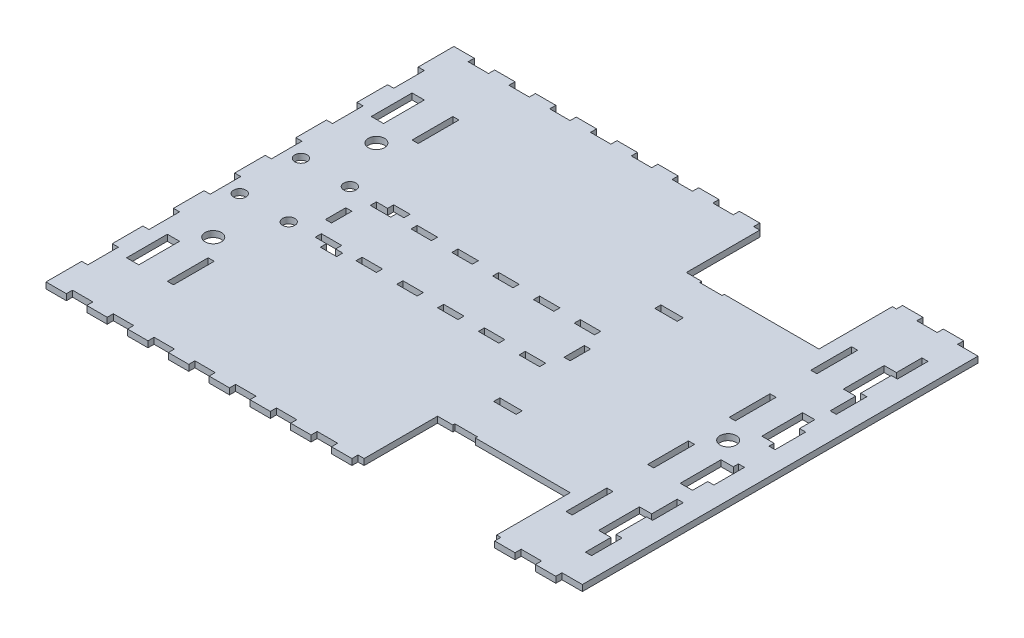
SolidWorks part; units mm, degrees
ref_plane "Front Plane" through (0, 0, 0) normal (0, 0, 1) x (1, 0, 0)
ref_plane "Top Plane" through (0, 0, 0) normal (0, 1, 0) x (1, 0, 0)
ref_plane "Right Plane" through (0, 0, 0) normal (1, 0, 0) x (0, 0, -1)
sketch "Sketch3" plane through (0, 0, 0) normal (0, 1, 0) x (1, 0, 0)
  line L0 (0, 0) -> (-300, 0) construction
  line L1 (-300, -97) -> (-300, 97)
  line L2 (-290, 100) -> (-300, 100)
  line L3 (-290, 97) -> (-290, 100)
  line L4 (-280, 97) -> (-290, 97)
  line L5 (-300, 100) -> (-300, 97)
  line L6 (-270, 100) -> (-280, 100)
  line L7 (-270, 97) -> (-270, 100)
  line L8 (-260, 97) -> (-270, 97)
  line L9 (-280, 100) -> (-280, 97)
  line L10 (-250, 100) -> (-260, 100)
  line L11 (-250, 97) -> (-250, 100)
  line L12 (-240, 97) -> (-250, 97)
  line L13 (-260, 100) -> (-260, 97)
  line L14 (-150, -100) -> (-150, 100) construction
  line L15 (-230, 100) -> (-240, 100)
  line L16 (-230, 97) -> (-230, 100)
  line L17 (-220, 97) -> (-230, 97)
  line L18 (-240, 100) -> (-240, 97)
  line L19 (-210, 100) -> (-220, 100)
  line L20 (-210, 97) -> (-210, 100)
  line L21 (-200, 97) -> (-210, 97)
  line L22 (-40, 97) -> (-40, -97)
  line L23 (-50, 37.5) -> (-53, 37.5)
  line L24 (-50, 7.5) -> (-53, 7.5)
  line L25 (-50, -45.947) -> (-50, 45.947) construction
  line L26 (-247, 37.5) -> (-250, 37.5) construction
  line L27 (-247, 7.5) -> (-250, 7.5) construction
  line L28 (-247, 48.5) -> (-247, -48.5) construction
  line L29 (-247, 48.5) -> (-223, 48.5) construction
  line L30 (-223, 48.5) -> (-223, -48.5) construction
  line L31 (-210, 15) -> (-90, 15) construction
  line L32 (-90, 15) -> (-90, 5) construction
  line L33 (-50, 7.5) -> (-50, 22.5)
  line L34 (-220, 100) -> (-220, 97)
  line L35 (-190, 100) -> (-200, 100)
  line L36 (-190, 97) -> (-190, 100)
  line L37 (-180, 97) -> (-190, 97)
  line L38 (-200, 100) -> (-200, 97)
  line L39 (-170, 100) -> (-180, 100)
  line L40 (-170, 97) -> (-170, 100)
  line L41 (-160, 97) -> (-170, 97)
  line L42 (-180, 100) -> (-180, 97)
  line L43 (-150, 100) -> (-160, 100)
  line L44 (-150, 97) -> (-150, 100)
  line L45 (-140, 97) -> (-150, 97)
  line L46 (-160, 100) -> (-160, 97)
  line L47 (-130, 100) -> (-140, 100)
  line L48 (-130, 97) -> (-130, 100)
  line L49 (-120, 97) -> (-130, 97)
  line L50 (-140, 100) -> (-140, 97)
  line L51 (-110, 100) -> (-120, 100)
  line L52 (-110, 97) -> (-110, 100)
  line L53 (-100, 97) -> (-110, 97)
  line L54 (-120, 100) -> (-120, 97)
  line L55 (-90, 100) -> (-100, 100)
  line L56 (-90, 97) -> (-90, 100)
  line L57 (-80, 97) -> (-90, 97)
  line L58 (-100, 100) -> (-100, 97)
  line L59 (-70, 100) -> (-80, 100)
  line L60 (-70, 97) -> (-70, 100)
  line L61 (-60, 97) -> (-70, 97)
  line L62 (-80, 100) -> (-80, 97)
  line L63 (-50, 100) -> (-60, 100)
  line L64 (-50, 97) -> (-50, 100)
  line L65 (-40, 97) -> (-50, 97)
  line L66 (-60, 100) -> (-60, 97)
  line L67 (-50, 22.5) -> (-53, 22.5)
  line L68 (-210, -15) -> (-90, -15) construction
  line L69 (-53, 7.5) -> (-53, 22.5)
  line L70 (-50, 37.5) -> (-50, 52.5)
  line L71 (-50, 52.5) -> (-53, 52.5)
  line L72 (-53, 37.5) -> (-53, 52.5)
  line L73 (-50, 67.5) -> (-53, 67.5)
  line L74 (-50, 67.5) -> (-50, 82.5)
  line L75 (-50, 82.5) -> (-53, 82.5)
  line L76 (-60, -100) -> (-60, -97)
  line L77 (-40, -97) -> (-50, -97)
  line L78 (-50, -97) -> (-50, -100)
  line L79 (-50, -100) -> (-60, -100)
  line L80 (-80, -100) -> (-80, -97)
  line L81 (-60, -97) -> (-70, -97)
  line L82 (-70, -97) -> (-70, -100)
  line L83 (-70, -100) -> (-80, -100)
  line L84 (-100, -100) -> (-100, -97)
  line L85 (-80, -97) -> (-90, -97)
  line L86 (-90, -97) -> (-90, -100)
  line L87 (-90, -100) -> (-100, -100)
  line L88 (-120, -100) -> (-120, -97)
  line L89 (-100, -97) -> (-110, -97)
  line L90 (-110, -97) -> (-110, -100)
  line L91 (-110, -100) -> (-120, -100)
  line L92 (-140, -100) -> (-140, -97)
  line L93 (-120, -97) -> (-130, -97)
  line L94 (-130, -97) -> (-130, -100)
  line L95 (-130, -100) -> (-140, -100)
  line L96 (-160, -100) -> (-160, -97)
  line L97 (-140, -97) -> (-150, -97)
  line L98 (-150, -97) -> (-150, -100)
  line L99 (-150, -100) -> (-160, -100)
  line L100 (-180, -100) -> (-180, -97)
  line L101 (-160, -97) -> (-170, -97)
  line L102 (-170, -97) -> (-170, -100)
  line L103 (-170, -100) -> (-180, -100)
  line L104 (-200, -100) -> (-200, -97)
  line L105 (-180, -97) -> (-190, -97)
  line L106 (-190, -97) -> (-190, -100)
  line L107 (-190, -100) -> (-200, -100)
  line L108 (-247, -48.5) -> (-223, -48.5) construction
  line L109 (-247, 7.5) -> (-247, 22.5) construction
  line L110 (-220, -100) -> (-220, -97)
  line L111 (-53, 67.5) -> (-53, 82.5)
  line L112 (-53, -67.5) -> (-53, -82.5)
  line L113 (-50, -82.5) -> (-53, -82.5)
  line L114 (-200, -97) -> (-210, -97)
  line L115 (-210, -97) -> (-210, -100)
  line L116 (-210, -100) -> (-220, -100)
  line L117 (-240, -100) -> (-240, -97)
  line L118 (-220, -97) -> (-230, -97)
  line L119 (-230, -97) -> (-230, -100)
  line L120 (-230, -100) -> (-240, -100)
  line L121 (-50, -67.5) -> (-50, -82.5)
  line L122 (-260, -100) -> (-260, -97)
  line L123 (-240, -97) -> (-250, -97)
  line L124 (-250, -97) -> (-250, -100)
  line L125 (-250, -100) -> (-260, -100)
  line L126 (-280, -100) -> (-280, -97)
  line L127 (-260, -97) -> (-270, -97)
  line L128 (-270, -97) -> (-270, -100)
  line L129 (-270, -100) -> (-280, -100)
  line L130 (-300, -100) -> (-300, -97)
  line L131 (-210, 15) -> (-210, -15) construction
  line L132 (-253, -15) -> (-243, -15)
  line L133 (-233, -15) -> (-223, -15)
  line L188 (-247, 22.5) -> (-250, 22.5) construction
  line L189 (-250, 7.5) -> (-250, 22.5) construction
  line L190 (-247, 37.5) -> (-247, 52.5) construction
  line L191 (-247, 52.5) -> (-250, 52.5) construction
  line L192 (-250, 37.5) -> (-250, 52.5) construction
  line L193 (-247, 67.5) -> (-250, 67.5) construction
  line L194 (-247, 67.5) -> (-247, 82.5) construction
  line L195 (-247, 82.5) -> (-250, 82.5) construction
  line L196 (-250, 67.5) -> (-250, 82.5) construction
  line L197 (-250, -67.5) -> (-250, -82.5) construction
  line L198 (-247, -82.5) -> (-250, -82.5) construction
  line L199 (-247, -67.5) -> (-247, -82.5) construction
  line L200 (-247, -67.5) -> (-250, -67.5) construction
  line L201 (-250, -37.5) -> (-250, -52.5) construction
  line L202 (-247, -52.5) -> (-250, -52.5) construction
  line L203 (-247, -37.5) -> (-247, -52.5) construction
  line L204 (-250, -7.5) -> (-250, -22.5) construction
  line L205 (-247, -22.5) -> (-250, -22.5) construction
  line L206 (-247, -7.5) -> (-247, -22.5) construction
  line L207 (-247, -7.5) -> (-250, -7.5) construction
  line L208 (-247, -37.5) -> (-250, -37.5) construction
  line L209 (-50, -67.5) -> (-53, -67.5)
  line L210 (-53, -37.5) -> (-53, -52.5)
  line L211 (-50, -52.5) -> (-53, -52.5)
  line L212 (-50, -37.5) -> (-50, -52.5)
  line L213 (-53, -7.5) -> (-53, -22.5)
  line L214 (-50, -22.5) -> (-53, -22.5)
  line L215 (-50, -7.5) -> (-50, -22.5)
  line L216 (-50, -7.5) -> (-53, -7.5)
  line L217 (-50, -37.5) -> (-53, -37.5)
  line L218 (-210, 0) -> (-258, 0)
  line L219 (-258, -5) -> (-255, -5)
  line L220 (-163, 15) -> (-173, 15)
  line L221 (-243, -12) -> (-243, -15)
  line L222 (-143, 15) -> (-143, 12)
  line L223 (-173, -15) -> (-173, -12)
  line L224 (-163, -15) -> (-173, -15)
  line L225 (-183, 12) -> (-183, 15)
  line L226 (-153, 15) -> (-153, 12)
  line L227 (-163, -12) -> (-163, -15)
  line L228 (-243, -12) -> (-253, -12)
  line L229 (-193, -15) -> (-193, -12)
  line L230 (-258, 5) -> (-255, 5)
  line L231 (-280, -97) -> (-290, -97)
  line L232 (-290, -97) -> (-290, -100)
  line L233 (-290, -100) -> (-300, -100)
  line L234 (-143, 15) -> (-153, 15)
  line L235 (-203, -12) -> (-213, -12)
  line L236 (-213, -15) -> (-213, -12)
  line L237 (-233, -15) -> (-233, -12)
  line L238 (-138, 5) -> (-141, 5)
  line L239 (-243, 12) -> (-243, 15)
  line L240 (-223, 12) -> (-223, 15)
  line L241 (-203, 12) -> (-213, 12)
  line L242 (-153, -15) -> (-153, -12)
  line L243 (-253, 15) -> (-253, 12)
  line L244 (-163, 12) -> (-163, 15)
  line L245 (-141, 5) -> (-141, -5)
  line L246 (-143, -15) -> (-143, -12)
  line L247 (-223, -12) -> (-233, -12)
  line L248 (-258, 15) -> (-258, -15) construction
  line L249 (-233, 15) -> (-233, 12)
  line L250 (-223, 15) -> (-233, 15)
  line L251 (-138, -5) -> (-141, -5)
  line L252 (-183, -15) -> (-193, -15)
  line L253 (-203, 15) -> (-213, 15)
  line L254 (-138, 5) -> (-138, -5)
  line L255 (-258, -15) -> (-138, -15) construction
  line L256 (-255, 5) -> (-255, -5)
  line L257 (-258, 5) -> (-258, -5)
  line L258 (-258, 15) -> (-138, 15) construction
  line L259 (-193, 15) -> (-193, 12)
  line L260 (-163, 12) -> (-173, 12)
  line L261 (-203, -15) -> (-213, -15)
  line L262 (-243, 12) -> (-253, 12)
  line L263 (-183, 15) -> (-193, 15)
  line L264 (-143, 12) -> (-153, 12)
  line L265 (-243, 15) -> (-253, 15)
  line L266 (-213, 15) -> (-213, 12)
  line L267 (-173, 15) -> (-173, 12)
  line L268 (-223, -12) -> (-223, -15)
  line L269 (-143, -12) -> (-153, -12)
  line L270 (-143, -15) -> (-153, -15)
  line L271 (-183, -12) -> (-193, -12)
  line L272 (-203, -12) -> (-203, -15)
  line L273 (-203, 12) -> (-203, 15)
  line L274 (-183, -12) -> (-183, -15)
  line L275 (-253, -15) -> (-253, -12)
  line L276 (-223, 12) -> (-233, 12)
  line L277 (-183, 12) -> (-193, 12)
  line L278 (-163, -12) -> (-173, -12)
  circle A0 centre (-290, 15) radius 3
  circle A1 centre (-266, 15) radius 3
  circle A2 centre (-266, -15) radius 3
  circle A3 centre (-290, -15) radius 3
  point P31 (-250, 36)
  point P80 (-91.5, 0)
  point P82 (-150, 0)
  point P126 (-223, 0)
  point P128 (-250, 18)
  point P129 (-50, 0)
  point P150 (-150, -15)
  point P151 (-150, 15)
  point P183 (-208.5, 0)
  point P212 (-223, 18)
  point P218 (-223, 36)
  point P235 (-198, -15)
  point P236 (-198, 15)
  dimension "D17" = 6
  dimension "D18" = 6
  dimension "D1" = 300
  dimension "D4" = 7.5
  dimension "D5" = 100
  dimension "D6" = 97
  dimension "D7" = 15
  dimension "D8" = 97
  dimension "D9" = 3
  dimension "D10" = 3
  dimension "D11" = 48.5
  dimension "D12" = 24
  dimension "D13" = 60
  dimension "D14" = 15
  dimension "D15" = 24
  dimension "D16" = 15
  dimension "D19" = 194
  dimension "D20" = 10
  dimension "D21" = 3
  dimension "D22" = 7.5
  dimension "D23" = 15
  dimension "D24" = 3
  dimension "D25" = 3
  dimension "D26" = 48
  dimension "D31" = 10
  dimension "D36" = 3
extrude "Boss-Extrude1" add sketch "Sketch3" along normal blind 3 contours L1 L116 L115 L107 L106 L83 L82 L79 L95 L98 L99 L91 L90 L86 region at (-170.2364, 0, 0)
sketch "Sketch5" plane through (0, 3, 0) normal (0, 1, 0) x (1, 0, 0)
  line L0 (-82, 0) -> (-82, 61) construction
  line L1 (-134, -60) -> (-134, -41)
  line L2 (-82, 61) -> (-128.5, 61)
  line L3 (-82, 61) -> (-82, 97)
  line L4 (-82, 97) -> (-147, 97)
  line L5 (-147, 61) -> (-147, 97)
  line L7 (-110, 100) -> (-120, 100) construction
  line L8 (-82, 0) -> (-300, 0) construction
  line L9 (-300, 100) -> (-300, -100) construction
  line L10 (-147, -61) -> (-147, -97)
  line L11 (-82, -97) -> (-147, -97)
  line L12 (-82, -61) -> (-82, -97)
  line L13 (-82, -61) -> (-128.5, -61)
  line L14 (-114.5, -61) -> (-114.5, -41) construction
  line L15 (-114.5, -41) -> (-128.5, -41) construction
  line L16 (-128.5, -41) -> (-128.5, -38)
  line L17 (-128.5, -38) -> (-139.5, -38)
  line L18 (-139.5, -38) -> (-139.5, -41)
  line L19 (-139.5, -41) -> (-128.5, -41)
  line L20 (-128.5, -61) -> (-128.5, -60)
  line L21 (-128.5, -60) -> (-139.5, -60)
  line L22 (-139.5, -60) -> (-139.5, -61)
  line L23 (-139.5, -61) -> (-147, -61)
  line L24 (-114.5, 41) -> (-128.5, 41) construction
  line L25 (-114.5, 61) -> (-114.5, 41) construction
  line L26 (-139.5, 60) -> (-139.5, 61)
  line L27 (-128.5, 60) -> (-139.5, 60)
  line L28 (-128.5, 61) -> (-128.5, 60)
  line L29 (-139.5, 41) -> (-128.5, 41)
  line L30 (-139.5, 38) -> (-139.5, 41)
  line L31 (-128.5, 38) -> (-139.5, 38)
  line L32 (-128.5, 41) -> (-128.5, 38)
  line L33 (-139.5, 61) -> (-147, 61)
  dimension "D1" = 19
  dimension "D2" = 36
  dimension "D3" = 3
  dimension "D5" = 14
  dimension "D6" = 3
  dimension "D7" = 11
  dimension "D9" = 1
extrude "Cut-Extrude2" cut sketch "Sketch5" against normal blind 10 contours L5 L2 L3 L4 | L12 L13 L10 L11 | L31 L30 L29 L32 | L17 L18 L19 L16 region at (-114.5912, 3, 78.9134) region at (-114.5912, 3, -78.9134) body kept at (-300, 0, -100)
sketch "Croquis1" plane through (0, 3, 0) normal (0, 1, 0) x (1, 0, 0)
  line L0 (-300, -67.5) -> (-300, -82.5)
  line L25 (-300, 100) -> (-300, -100) construction
  line L26 (-300, 37.5) -> (-300, 52.5)
  line L27 (-297, 37.5) -> (-300, 37.5)
  line L28 (-297, 7.5) -> (-300, 7.5)
  line L29 (-300, -7.5) -> (-297, -7.5)
  line L30 (-297, -22.5) -> (-300, -22.5)
  line L31 (-297, -7.5) -> (-297, -22.5)
  line L32 (-297, 82.5) -> (-297, 67.5)
  line L33 (-300, -22.5) -> (-300, -7.5)
  line L34 (-297, -37.5) -> (-297, -52.5)
  line L35 (-297, 67.5) -> (-300, 67.5)
  line L36 (-300, 67.5) -> (-300, 82.5)
  line L37 (-297, 52.5) -> (-297, 37.5)
  line L38 (-300, 22.5) -> (-297, 22.5)
  line L39 (-300, -37.5) -> (-297, -37.5)
  line L40 (-297, -52.5) -> (-300, -52.5)
  line L41 (-300, 52.5) -> (-297, 52.5)
  line L42 (-300, -52.5) -> (-300, -37.5)
  line L43 (-300, 82.5) -> (-297, 82.5)
  line L44 (-297, 22.5) -> (-297, 7.5)
  line L45 (-300, 7.5) -> (-300, 22.5)
  line L46 (-300, -67.5) -> (-297, -67.5)
  line L47 (-297, -67.5) -> (-297, -82.5)
  line L48 (-297, -82.5) -> (-300, -82.5)
  dimension "D1" = 15
  dimension "D2" = 15
extrude "Cortar-Extruir1" cut sketch "Croquis1" against normal blind 10
sketch "Croquis2" plane through (0, 3, 0) normal (0, 1, 0) x (1, 0, 0)
  line L0 (-40, 0) -> (-53, 0) construction
  line L1 (-40, 97) -> (-40, -97) construction
  line L2 (-53, 10) -> (-53, -10) construction
  line L3 (-53, -7.5) -> (-53, -22.5) construction
  line L4 (-53, -10) -> (-59, -10)
  line L5 (-59, -10) -> (-59, -30)
  line L6 (-59, -30) -> (-53, -30)
  line L7 (-53, -30) -> (-53, -10)
  line L8 (-53, -30) -> (-53, -50) construction
  line L9 (-53, -37.5) -> (-53, -52.5) construction
  line L10 (-53, -50) -> (-59, -50)
  line L11 (-59, -50) -> (-59, -70)
  line L12 (-59, -70) -> (-53, -70)
  line L13 (-53, -67.5) -> (-53, -82.5) construction
  line L14 (-53, -70) -> (-53, -50)
  line L15 (-53, 30) -> (-53, 50) construction
  line L16 (-53, 70) -> (-53, 50)
  line L17 (-59, 70) -> (-53, 70)
  line L18 (-59, 50) -> (-59, 70)
  line L19 (-53, 50) -> (-59, 50)
  line L20 (-53, 30) -> (-53, 10)
  line L21 (-59, 30) -> (-53, 30)
  line L22 (-59, 10) -> (-59, 30)
  line L23 (-53, 10) -> (-59, 10)
  line L24 (-59, 70) -> (-72, 70) construction
  line L25 (-72, 70) -> (-75, 70)
  line L26 (-72, 70) -> (-72, 50)
  line L27 (-72, 50) -> (-75, 50)
  line L28 (-75, 50) -> (-75, 70)
  line L29 (-72, 30) -> (-75, 30)
  line L30 (-75, 30) -> (-75, 10)
  line L31 (-75, 10) -> (-72, 10)
  line L32 (-72, 10) -> (-72, 30)
  line L33 (-72, -10) -> (-75, -10)
  line L34 (-75, -10) -> (-75, -30)
  line L35 (-75, -30) -> (-72, -30)
  line L36 (-72, -30) -> (-72, -10)
  line L37 (-72, -50) -> (-75, -50)
  line L38 (-75, -50) -> (-75, -70)
  line L39 (-75, -70) -> (-72, -70)
  line L40 (-72, -70) -> (-72, -50)
  line L41 (-266, 15) -> (-243.49, 15) construction
  line L43 (-243.49, 18) -> (-247.49, 18)
  line L44 (-247.49, 18) -> (-247.49, 15)
  line L45 (-290.5, 30) -> (-290.5, 50) construction
  line L46 (-290.5, -30) -> (-290.5, -50) construction
  line L47 (-247.49, 15) -> (-239.49, 15)
  line L48 (-239.49, 15) -> (-239.49, 18)
  line L49 (-270.5, -70) -> (-270.5, -50)
  line L50 (-267.5, -70) -> (-270.5, -70)
  line L51 (-267.5, -50) -> (-267.5, -70)
  line L52 (-270.5, -50) -> (-267.5, -50)
  line L53 (-239.49, 18) -> (-243.49, 18)
  line L55 (-239.49, -18) -> (-243.49, -18)
  line L56 (-239.49, -15) -> (-239.49, -18)
  line L57 (-247.49, -15) -> (-239.49, -15)
  line L58 (-247.49, -18) -> (-247.49, -15)
  line L59 (-243.49, -18) -> (-247.49, -18)
  line L61 (-267.5, 50) -> (-267.5, 70)
  line L62 (-270.5, 50) -> (-267.5, 50)
  line L63 (-270.5, 70) -> (-270.5, 50)
  line L64 (-270.5, 70) -> (-267.5, 70)
  line L69 (-290.5, 50) -> (-284.5, 50)
  line L70 (-284.5, 50) -> (-284.5, 70)
  line L71 (-284.5, 70) -> (-290.5, 70)
  line L72 (-290.5, 70) -> (-290.5, 50)
  line L73 (-290.5, -70) -> (-290.5, -50)
  line L74 (-284.5, -70) -> (-290.5, -70)
  line L75 (-284.5, -50) -> (-284.5, -70)
  line L76 (-290.5, -50) -> (-284.5, -50)
  circle A0 centre (-65.5, 0) radius 4
  circle A3 centre (-278, -40) radius 4
  circle A4 centre (-278, 40) radius 4
  dimension "D8" = 8
  dimension "D11" = 8
  dimension "D12" = 8
  dimension "D1" = 10
  dimension "D2" = 6
  dimension "D3" = 20
  dimension "D4" = 20
  dimension "D5" = 13
  dimension "D6" = 3
  dimension "D7" = 20
  dimension "D9" = 14
  dimension "D10" = 22.51
  dimension "D13" = 3
  dimension "D14" = 4
  dimension "D15" = 8
extrude "Cortar-Extruir2" cut sketch "Croquis2" against normal blind 10
